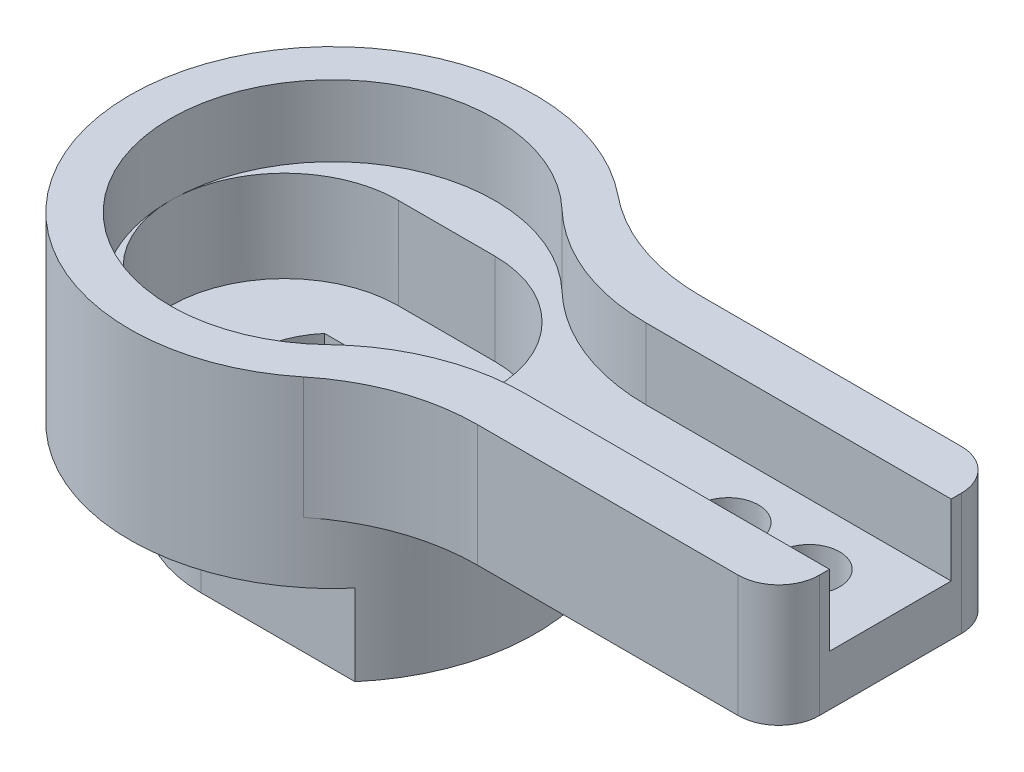
SolidWorks part; units mm, degrees
ref_plane "Front Plane" through (0, 0, 0) normal (0, 0, 1) x (1, 0, 0)
ref_plane "Top Plane" through (0, 0, 0) normal (0, 1, 0) x (1, 0, 0)
ref_plane "Right Plane" through (0, 0, 0) normal (1, 0, 0) x (0, 0, -1)
sketch "Sketch1" plane through (0, 0, 0) normal (0, 1, 0) x (1, 0, 0)
  circle A0 centre (0, 0) radius 6.5
extrude "Boss-Extrude1" add sketch "Sketch1" along normal blind 8
sketch "Sketch14" plane through (0, 8, 0) normal (0, 1, 0) x (1, 0, 0)
  circle A0 centre (0, 0) radius 10
extrude "Boss-Extrude6" add sketch "Sketch14" against normal blind 4
sketch "Sketch15" plane through (0, 8, 0) normal (0, 1, 0) x (1, 0, 0)
  circle A0 centre (0, 0) radius 5.625
extrude "Cut-Extrude7" cut sketch "Sketch15" against normal blind 3
sketch "Sketch2" plane through (0, 0, 0) normal (0, 1, 0) x (1, 0, 0)
  circle A0 centre (0, 0) radius 4
extrude "Cut-Extrude1" cut sketch "Sketch2" along normal up to next
sketch "Sketch3" plane through (0, 0, 0) normal (0, 1, 0) x (1, 0, 0)
  line L1 (-5.0382, -2.625) -> (5.0382, -2.625)
  line L2 (-5.0382, -2.625) -> (-5.0382, 2.625) construction
  line L3 (-5.0382, 2.625) -> (5.0382, 2.625)
  line L4 (5.0382, -2.625) -> (5.0382, 2.625) construction
  line L5 (-5.0382, -2.625) -> (5.0382, 2.625) construction
  line L6 (-5.0382, 2.625) -> (5.0382, -2.625) construction
  arc A0 (-5.0382, 2.625) -> (5.0382, 2.625) centre (0, 0) cw
  arc A1 (-5.0382, -2.625) -> (5.0382, -2.625) centre (0, 0) ccw
  point P0 (0, 0)
  dimension "D1" = 5.25
extrude "Boss-Extrude2" add sketch "Sketch3" along normal blind 8
sketch "Sketch4" plane through (0, 8, 0) normal (0, 1, 0) x (1, 0, 0)
  circle A0 centre (0, 0) radius 10
extrude "Boss-Extrude3" add sketch "Sketch4" along normal blind 5
sketch "Sketch6" plane through (0, 13, 0) normal (0, 1, 0) x (1, 0, 0)
  line L0 (27.5, -5.5) -> (-7.5, -5.5)
  line L1 (27.5, -5.5) -> (27.5, 5.5)
  line L2 (-7.5, -5.5) -> (-7.5, 5.5)
  line L3 (27.5, 5.5) -> (-7.5, 5.5)
  line L4 (27.5, -5.5) -> (-7.5, 5.5) construction
  line L5 (-7.5, -5.5) -> (27.5, 5.5) construction
  point P1 (10, 0)
  dimension "D1" = 11
  dimension "D2" = 35
extrude "Boss-Extrude4" add sketch "Sketch6" against normal blind 6
sketch "Sketch7" plane through (0, 13, 0) normal (0, 1, 0) x (1, 0, 0)
  circle A0 centre (0, 0) radius 8
extrude "Cut-Extrude2" cut sketch "Sketch7" against normal blind 3.5
sketch "Sketch8" plane through (0, 13, 0) normal (0, 1, 0) x (1, 0, 0)
  line L0 (29.1729, -3) -> (-0.8271, -3)
  line L1 (29.1729, -3) -> (29.1729, 3)
  line L2 (-0.8271, -3) -> (-0.8271, 3)
  line L3 (29.1729, 3) -> (-0.8271, 3)
  line L4 (29.1729, -3) -> (-0.8271, 3) construction
  line L5 (-0.8271, -3) -> (29.1729, 3) construction
  point P1 (14.1729, 0)
  dimension "D1" = 6
  dimension "D2" = 30
extrude "Cut-Extrude3" cut sketch "Sketch8" against normal blind 3.5
fillet "Fillet1" radius 10 4 edges at (7.4162, 11.25, 3) (7.4162, 11.25, -3) (8.3516, 10, 5.5) (8.3516, 10, -5.5)
fillet "Fillet2" radius 2 2 edges at (27.5, 10, 5.5) (27.5, 10, -5.5)
sketch "Sketch9" plane through (0, 9.5, 0) normal (0, 1, 0) x (1, 0, 0)
  line L0 (0, 0) -> (19.5, 0) construction
  line L1 (19.5, 0) -> (23.5, 0) construction
  circle A0 centre (19.5, 0) radius 1.5
  circle A1 centre (23.5, 0) radius 1.5
extrude "Cut-Extrude4" cut sketch "Sketch9" against normal up to next
sketch "Sketch16" plane through (0, 9.5, 0) normal (0, 1, 0) x (1, 0, 0)
  line L0 (-2.375, 0) -> (2.375, 0) construction
  line L1 (-2.375, 5.625) -> (2.375, 5.625)
  line L2 (-2.375, -5.625) -> (2.375, -5.625)
  arc A1 (-2.375, 5.625) -> (-2.375, -5.625) centre (-2.375, 0) ccw
  arc A2 (2.375, -5.625) -> (2.375, 5.625) centre (2.375, 0) ccw
  point P3 (0, 0)
extrude "Cut-Extrude8" cut sketch "Sketch16" against normal up to vertex (4.5 mm away) up to point (-3.0182, 5, -2.625)
sketch "Sketch19" plane through (0, 4, 0) normal (0, -1, 0) x (1, 0, 0)
  line L0 (0, 6.5) -> (7.5993, 6.5)
  line L1 (0, -6.5) -> (7.5993, -6.5)
  line L2 (0, 6.5) -> (0, 6)
  line L3 (0, -6.5) -> (0, -6)
  circle A0 centre (0, 0) radius 6.5 construction
  arc A1 (6.3196, -7.75) -> (6.3196, 7.75) centre (0, 0) ccw construction
  circle A2 centre (0, 0) radius 6.5 construction
  circle A3 centre (0, 0) radius 10 construction
  arc A4 (0, 6) -> (0, -6) centre (0, 0) cw
  arc A5 (7.5993, 6.5) -> (7.5993, -6.5) centre (0, 0) cw
extrude "Boss-Extrude8" add sketch "Sketch19" along normal up to surface (4 mm away) up to face at (0, 0, 0)
